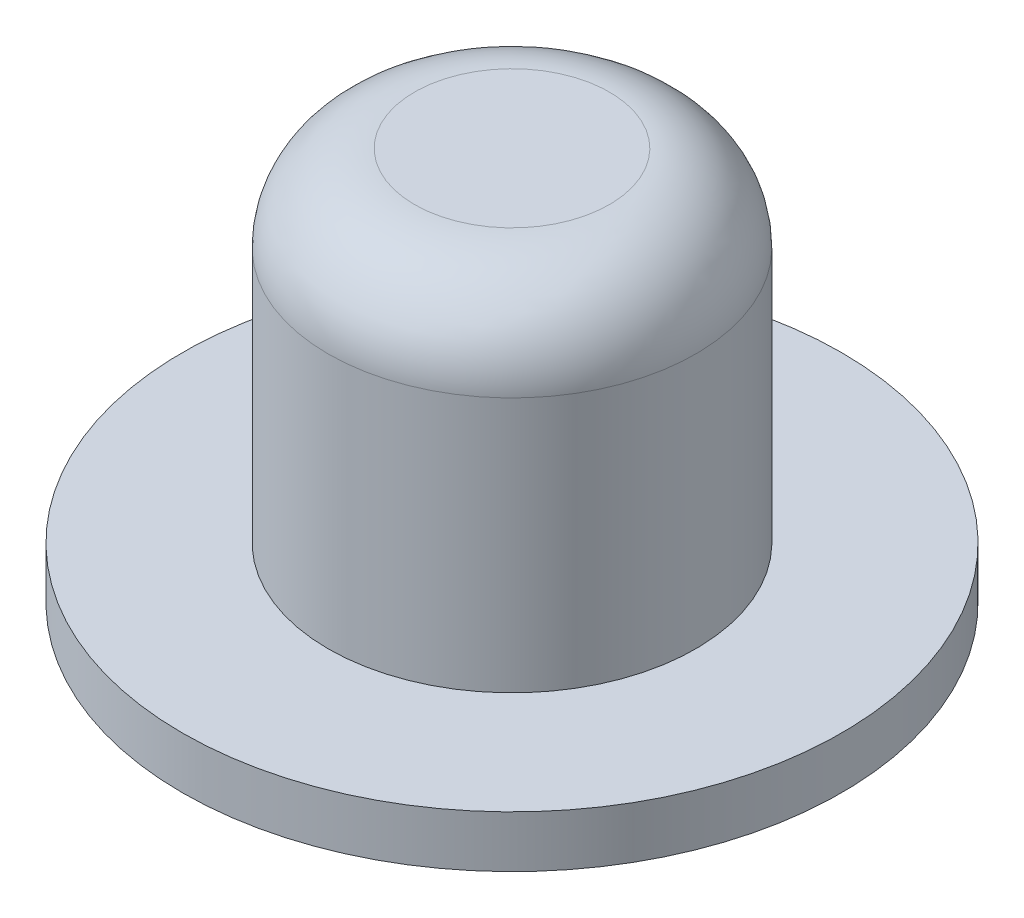
SolidWorks part; units mm, degrees
ref_plane "Front Plane" through (0, 0, 0) normal (0, 0, 1) x (1, 0, 0)
ref_plane "Top Plane" through (0, 0, 0) normal (0, 1, 0) x (1, 0, 0)
ref_plane "Right Plane" through (0, 0, 0) normal (1, 0, 0) x (0, 0, -1)
sketch "Sketch1" plane through (0, 0, 0) normal (0, 1, 0) x (1, 0, 0)
  circle A0 centre (0, 0) radius 19.1
  circle A1 centre (0, 0) radius 10.65
  dimension "D1" = 38.2
  dimension "D2" = 21.3
extrude "Boss-Extrude1" add sketch "Sketch1" along normal blind 3
extrude "Boss-Extrude2" add sketch "Sketch1<2>" along normal blind 22.8 contours A1 region at (0, 0, 0)
sketch "Sketch1<2>" plane through (0, 0, 0) normal (0, 1, 0) x (1, 0, 0) same geometry as "Sketch1"
fillet "Fillet1" radius 5 1 edges at (0, 22.8, 10.65)
